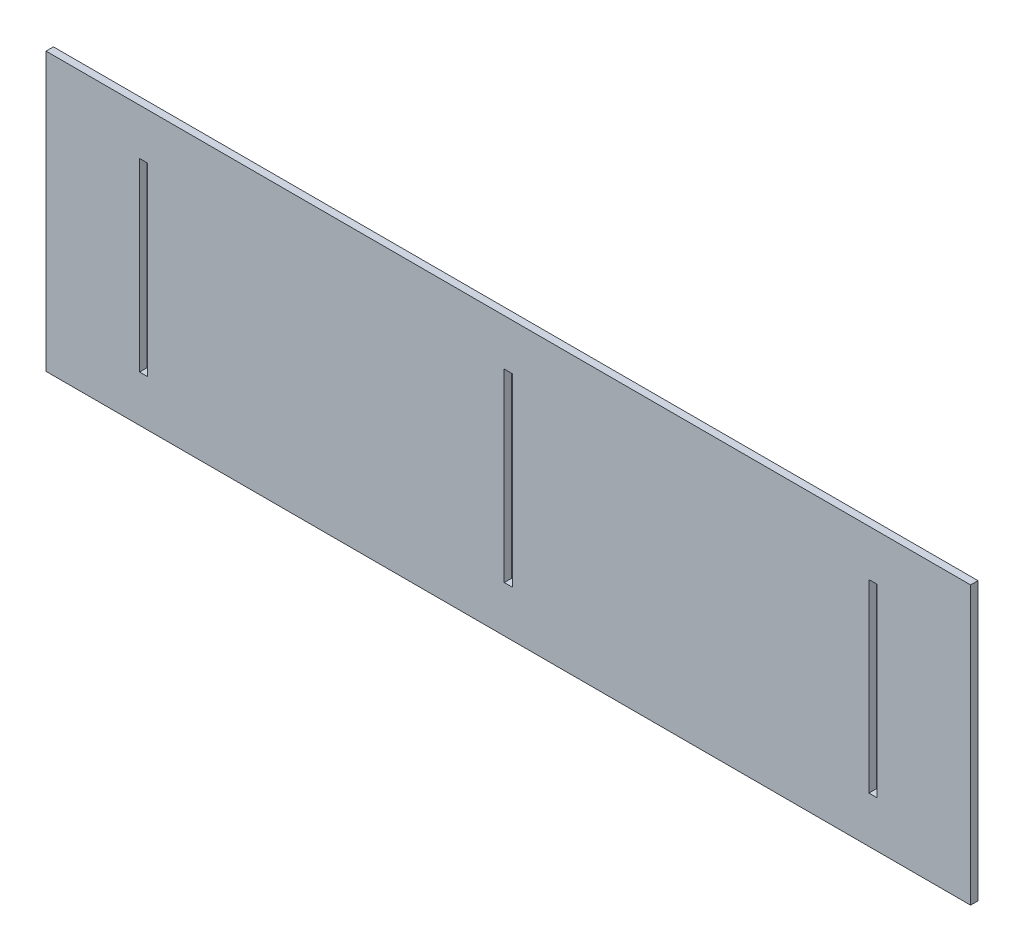
SolidWorks part; units mm, degrees
ref_plane "前视基准面" through (0, 0, 0) normal (0, 0, 1) x (1, 0, 0)
ref_plane "上视基准面" through (0, 0, 0) normal (0, 1, 0) x (1, 0, 0)
ref_plane "右视基准面" through (0, 0, 0) normal (1, 0, 0) x (0, 0, -1)
sketch "草图2" plane through (0, 0, 0) normal (0, 0, 1) x (1, 0, 0)
  line L1 (-73.6818, 78.3847) -> (176.3182, 78.3847)
  line L2 (-73.6818, 78.3847) -> (-73.6818, 3.3847)
  line L3 (-73.6818, 3.3847) -> (176.3182, 3.3847)
  line L4 (176.3182, 78.3847) -> (176.3182, 3.3847)
  dimension "D1" = 250
  dimension "D2" = 75
sketch "草图4" plane through (0, 0, 0) normal (0, 0, 1) x (1, 0, 0)
  line L5 (-73.6818, 78.3847) -> (176.3182, 78.3847) construction
  line L6 (-73.6818, 78.3847) -> (-73.6818, 3.3847) construction
  line L7 (51.3182, 96.8277) -> (51.3182, 60.5853) construction
  line L8 (151.0182, 40.8847) -> (148.8182, 40.8847) construction
  line L9 (149.9182, 15.8847) -> (149.9182, 65.8847) construction
  line L10 (148.8182, 65.8847) -> (148.8182, 15.8847)
  line L11 (-48.3818, 65.8847) -> (-46.1818, 65.8847)
  line L12 (-48.3818, 65.8847) -> (-48.3818, 15.8847)
  line L13 (-48.3818, 15.8847) -> (-46.1818, 15.8847)
  line L14 (-46.1818, 65.8847) -> (-46.1818, 15.8847)
  line L15 (-47.2818, 15.8847) -> (-47.2818, 65.8847) construction
  line L16 (-48.3818, 40.8847) -> (-46.1818, 40.8847) construction
  line L17 (50.2182, 65.8847) -> (52.4182, 65.8847)
  line L18 (50.2182, 65.8847) -> (50.2182, 15.8847)
  line L19 (50.2182, 15.8847) -> (52.4182, 15.8847)
  line L20 (52.4182, 65.8847) -> (52.4182, 15.8847)
  line L21 (51.3182, 15.8847) -> (51.3182, 65.8847) construction
  line L22 (50.2182, 40.8847) -> (52.4182, 40.8847) construction
  line L26 (151.0182, 15.8847) -> (148.8182, 15.8847)
  line L27 (151.0182, 65.8847) -> (151.0182, 15.8847)
  line L28 (151.0182, 65.8847) -> (148.8182, 65.8847)
  line L29 (-73.6818, 3.3847) -> (176.3182, 3.3847) construction
  point P0 (51.3182, 78.3847)
  point P5 (0, 0)
  point P24 (51.3182, 40.8847)
  point P29 (-47.2818, 40.8847)
  point P34 (51.3182, 40.8847)
  point P35 (149.9182, 40.8847)
  dimension "D2" = 50
  dimension "D3" = 2.2
  dimension "D4" = 50
  dimension "D5" = 26.4
  dimension "D8" = 37.5
extrude "凸台-拉伸3" add sketch "草图2" along normal blind 2
extrude "切除-拉伸1" cut sketch "草图4" against normal blind 2 and the other way blind 2
